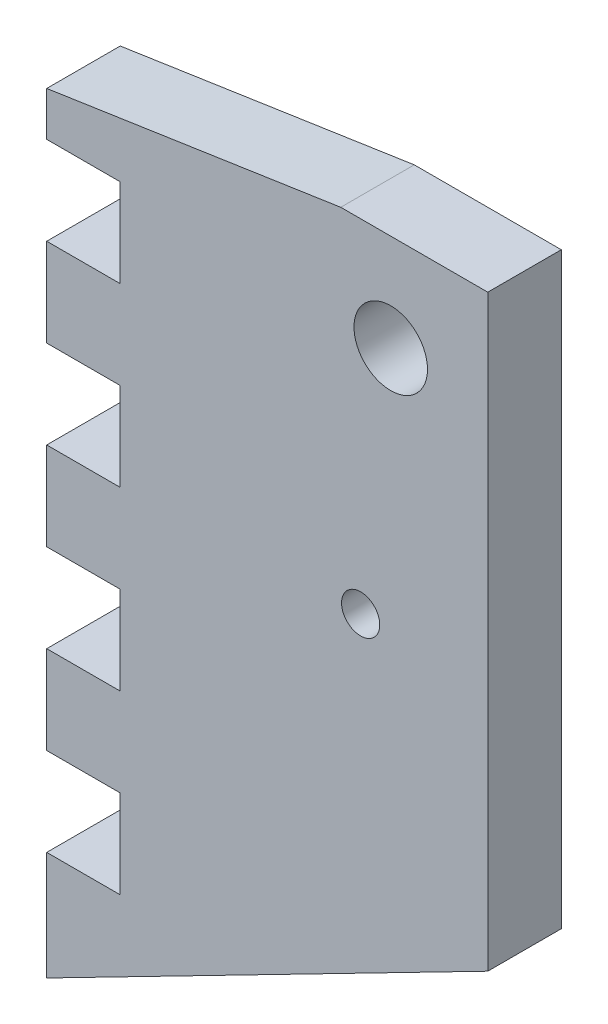
SolidWorks part; units mm, degrees
ref_plane "Front Plane" through (0, 0, 0) normal (0, 0, 1) x (1, 0, 0)
ref_plane "Top Plane" through (0, 0, 0) normal (0, 1, 0) x (1, 0, 0)
ref_plane "Right Plane" through (0, 0, 0) normal (1, 0, 0) x (0, 0, -1)
sketch "Sketch1" plane through (0, 0, 0) normal (0, 0, 1) x (1, 0, 0)
  line L0 (0, 0) -> (-38.1, 0)
  line L1 (0, 0) -> (0, -50.8)
  line L2 (-38.1, 0) -> (-38.1, -7.62)
  line L3 (-38.1, -7.62) -> (-31.75, -7.62)
  line L4 (-31.75, -7.62) -> (-31.75, -15.24)
  line L5 (-31.75, -15.24) -> (-38.1, -15.24)
  line L6 (-38.1, -45.72) -> (-38.1, -70.358)
  line L7 (-38.1, -15.24) -> (-38.1, -22.86)
  line L8 (-38.1, -22.86) -> (-31.75, -22.86)
  line L9 (-31.75, -22.86) -> (-31.75, -30.48)
  line L10 (-31.75, -30.48) -> (-38.1, -30.48)
  line L11 (-38.1, -30.48) -> (-38.1, -38.1)
  line L12 (-38.1, -38.1) -> (-31.75, -38.1)
  line L13 (-31.75, -38.1) -> (-31.75, -45.72)
  line L14 (-31.75, -45.72) -> (-38.1, -45.72)
  line L15 (-38.1, -70.358) -> (0, -50.8)
  circle A0 centre (-8.382, -8.382) radius 3.175
  dimension "D9" = 6.35
  dimension "D1" = 38.1
  dimension "D2" = 50.8
  dimension "D3" = 7.62
  dimension "D4" = 7.62
  dimension "D5" = 6.35
  dimension "D6" = 6.35
  dimension "D8" = 70.358
  dimension "D12" = 8.382
  dimension "D13" = 8.382
  dimension "D7" = 3
extrude "Boss-Extrude1" add sketch "Sketch1" along normal blind 6.35 contours L6 L15 L1 L0 L2 L3 L4 L5 L7 L8 L9 L10 L11 L12 L13 L14 A0 region at (-19.2374, -31.1465, 0)
sketch "Sketch2" plane through (0, 0, 0) normal (0, 0, -1) x (-1, 0, 0)
  line L5 (38.1, 0) -> (12.7, 0)
  line L6 (0, 0) -> (38.1, 0) construction
  line L7 (12.7, 0) -> (38.1, -3.81)
  line L8 (38.1, 0) -> (38.1, -7.62) construction
  line L9 (38.1, -3.81) -> (38.1, 0)
  dimension "D1" = 25.4
  dimension "D2" = 3.81
extrude "Cut-Extrude1" cut sketch "Sketch2" against normal blind 8.636
sketch "Sketch4" plane through (0, 0, 6.35) normal (0, 0, 1) x (1, 0, 0)
  line L0 (-38.1, -45.72) -> (-38.1, -53.34)
  line L1 (-38.1, -45.72) -> (-38.1, -70.358) construction
  line L2 (-38.1, -53.34) -> (-31.75, -53.34)
  line L3 (-31.75, -53.34) -> (-31.75, -60.96)
  line L4 (-31.75, -60.96) -> (-38.1, -60.96)
  line L5 (-38.1, -60.96) -> (-38.1, -53.34)
  line M18 (-38.1, -45.72) -> (-38.1, -70.358)
  dimension "D1" = 7.62
  dimension "D2" = 6.35
  dimension "D3" = 6.35
  dimension "D4" = 7.62
extrude "Cut-Extrude2" cut sketch "Sketch4" against normal through all contours L4 L3 L2 M18 region at (-34.925, -57.15, 6.35)
sketch "Sketch5" plane through (0, 0, 0) normal (0, 0, -1) x (-1, 0, 0)
  line L0 (8.382, -8.382) -> (10.9822, -29.559) construction
  line L1 (8.382, -8.382) -> (8.382, -39.2411) construction
  circle A0 centre (8.382, -8.382) radius 3.175 construction
  circle A1 centre (10.9822, -29.559) radius 1.651
  dimension "D1" = 21.336
  dimension "D2" = 7
extrude "Cut-Extrude4" cut sketch "Sketch5" against normal up to surface (6.35 mm away) up to face at (-5.207, -8.382, 6.35)
